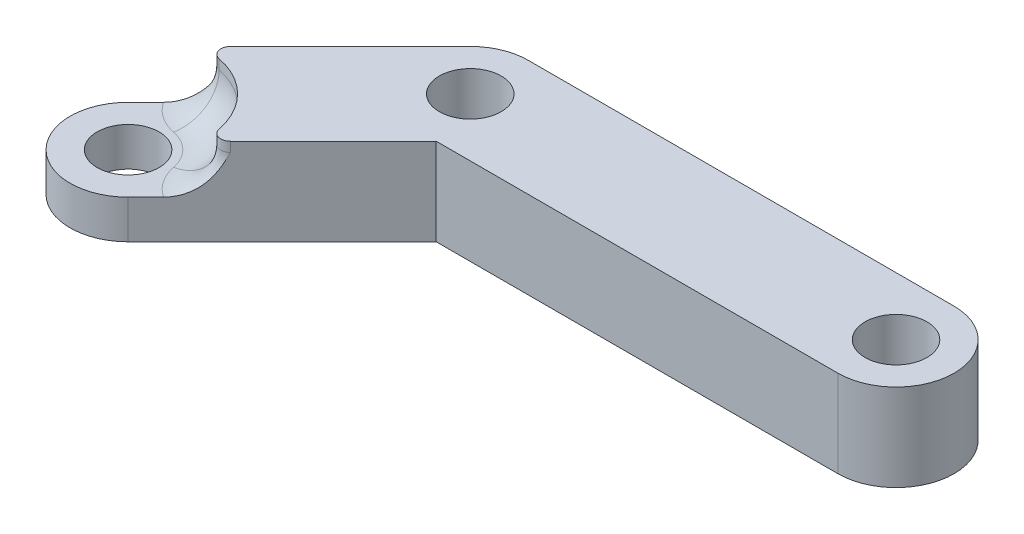
SolidWorks part; units mm, degrees
material "碳纤维"
ref_plane "前视基准面" through (0, 0, 0) normal (0, 0, 1) x (1, 0, 0)
ref_plane "上视基准面" through (0, 0, 0) normal (0, 1, 0) x (1, 0, 0)
ref_plane "右视基准面" through (0, 0, 0) normal (1, 0, 0) x (0, 0, -1)
other "Configuration Table"
ref_axis "基准轴1" through (-84.4094, 0, 0) along (1, 0, 0)
ref_axis "基准轴2" through (0, 52.75, 0) along (0, -1, 0)
ref_axis "基准轴3" through (0, 0, -84.5706) along (0, 0, 1)
sketch "草图1" plane through (0, 0, 0) normal (0, 1, 0) x (1, 0, 0)
  line L0 (0, 0) -> (22, 0) construction
  line L2 (0, 3) -> (22, 3)
  line L3 (0, -3) -> (22, -3)
  line L4 (0, 0) -> (-8.8388, -8.8388) construction
  line L5 (2.1213, -2.1213) -> (-6.7175, -10.9602)
  line L6 (-2.1213, 2.1213) -> (-10.9602, -6.7175)
  arc A0 (0, 3) -> (0, -3) centre (0, 0) ccw
  arc A1 (22, -3) -> (22, 3) centre (22, 0) ccw
  arc A2 (2.1213, -2.1213) -> (-2.1213, 2.1213) centre (0, 0) ccw
  arc A3 (-10.9602, -6.7175) -> (-6.7175, -10.9602) centre (-8.8388, -8.8388) ccw
  circle A4 centre (22, 0) radius 1.6
  circle A5 centre (0, 0) radius 1.6
  circle A6 centre (-8.8388, -8.8388) radius 1.6
  point P5 (11, 0)
  point P10 (-4.4194, -4.4194)
  dimension "D2" = 22
  dimension "D3" = 12.5
  dimension "D4" = 1.6
  dimension "D5" = 3
  dimension "D6" = 3
  dimension "D1" = 45
extrude "凸台-拉伸1" add sketch "草图1" along normal blind 4.5 contours A2 L5 L3 A1 L2 A4 | L5 A2 A0 L3 A5 | L6 A3 L5 L3 A0 A6 region at (2.6932, 0, -1.1156) region at (12.8136, 0, -0.0044) region at (-5.7749, 0, 5.7633)
sketch "草图2" plane through (0, 4.5, 0) normal (0, 1, 0) x (1, 0, 0)
  circle A0 centre (-8.8388, -8.8388) radius 4
  dimension "D1" = 4
extrude "切除-拉伸1" cut sketch "草图2" against normal blind 2.5
fillet "圆角1" radius 0.5 2 edges at (-9.0893, 3.25, 4.8467) (-4.8467, 3.25, 9.0893)
fillet "圆角2" radius 2 3 edges at (-4.5705, 2, 8.4393) (-8.4393, 2, 4.5705) (-6.0104, 2, 6.0104)
mirror "镜向1" [suppressed] about plane through (0, 0, 0) normal (0, 1, 0)
sketch "草图4" [suppressed] plane through (0, 0, 0) normal (0, 1, 0) x (1, 0, 0)
  circle A0 centre (0, 0) radius 25
  dimension "D1" = 25
extrude "切除-拉伸2" [suppressed] cut sketch "草图4" along normal blind 10
